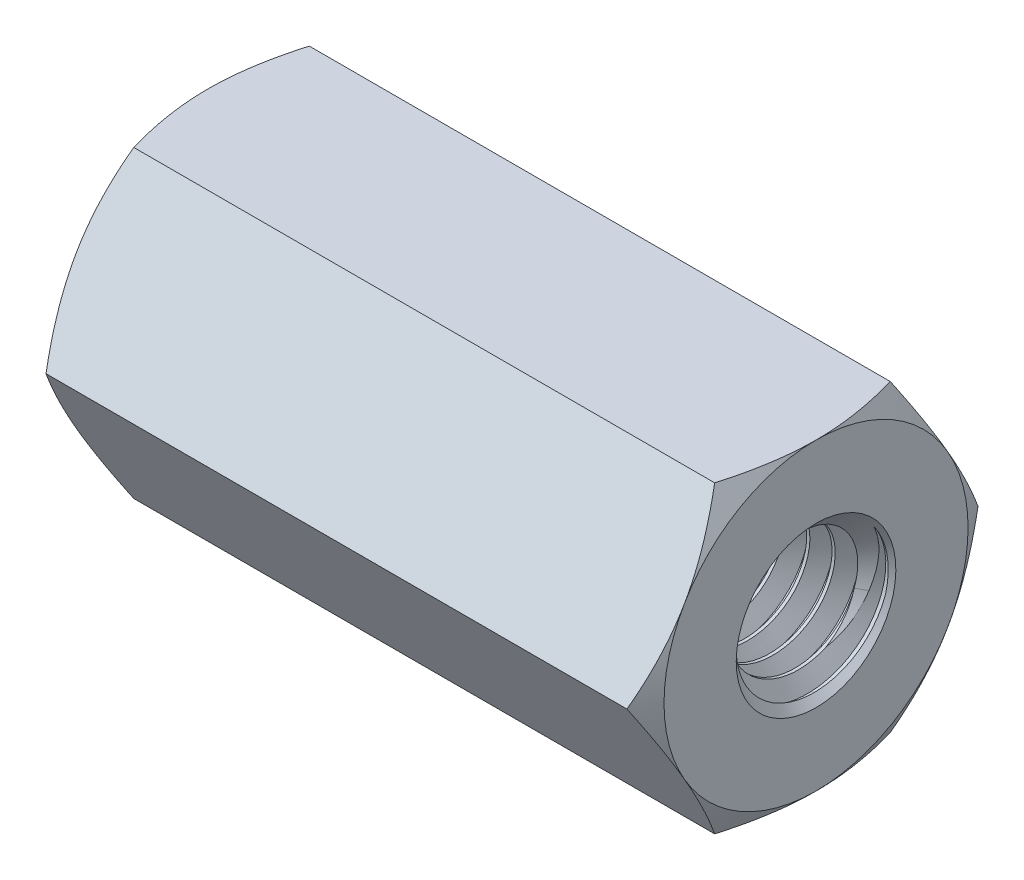
SolidWorks part; units mm, degrees
note: '?' marks a value the reader was unsure of.
material "6061-T6 (SS)"
ref_plane "Front Plane" through (0, 0, 0) normal (0, 0, 1) x (1, 0, 0)
ref_plane "Top Plane" through (0, 0, 0) normal (0, 1, 0) x (1, 0, 0)
ref_plane "Right Plane" through (0, 0, 0) normal (1, 0, 0) x (0, 0, -1)
sketch "Sketch1" plane through (0, 0, 0) normal (0, 0, 1) x (1, 0, 0)
  line L0 (0, 0) -> (12, 0) construction
  line L1 (0, 3) -> (0, -3) construction
  line L3 (0, 1.5) -> (-0.5, 1.5) construction
  line L4 (0, 3) -> (12, 3) construction
  point P6 (0, 0)
  dimension "Hex" = 6
  dimension "Pitch" = 0.5
  dimension "Thread OD" = 3
  dimension "Length" = 12
sketch "Sketch2" plane through (0, 0, 0) normal (1, 0, 0) x (0, 0, -1)
  line L0 (0, 0) -> (-1.0607, -1.0607) construction
  line L1 (1.7321, 3) -> (-1.7321, 3)
  line L2 (-1.7321, 3) -> (-3.4641, 0)
  line L3 (-3.4641, 0) -> (-1.7321, -3)
  line L4 (-1.7321, -3) -> (1.7321, -3)
  line L5 (1.7321, -3) -> (3.4641, 0)
  line L6 (3.4641, 0) -> (1.7321, 3)
  circle A0 centre (0, 0) radius 3 construction
  circle A1 centre (0, 0) radius 1.5 construction
  dimension "D1" = 45
extrude "Boss-Extrude1" add sketch "Sketch2" along normal up to vertex (12 mm away) up to point (12, 0, 0)
sketch "Sketch3" plane through (0, 0, 0) normal (0, 0, 1) x (1, 0, 0)
  line L0 (0, 1.575) -> (0.075, 1.5)
  line L1 (0, 0) -> (12, 0)
  line L2 (0, 0) -> (0, 1.575)
  line L3 (0.075, 1.5) -> (11.925, 1.5)
  line L4 (12, 0) -> (12, 1.575)
  line L9 (0, 3) -> (0, -3) construction
  line L11 (11.925, 1.5) -> (12, 1.575)
  line L12 (12, 3) -> (12, 0) construction
  line L13 (0, 0) -> (12, 0) construction
  line L14 (0, 1.5) -> (-0.5, 1.5) construction
  dimension "D1" = 3.15
  dimension "D2" = 45
revolve "Cut-Revolve1" cut sketch "Sketch3" angle 360 about L13
sketch "Sketch4" plane through (0, 0, 0) normal (-1, 0, 0) x (0, 0, 1)
  circle A0 centre (0, 0) radius 3
  circle A1 centre (0, 0) radius 3 construction
extrude "Cut-Extrude1" cut sketch "Sketch4" against normal through all draft 60 flip side to cut
sketch "Sketch5" plane through (12, 0, 0) normal (1, 0, 0) x (0, 0, -1)
  circle A0 centre (0, 0) radius 3
  circle A1 centre (0, 0) radius 3 construction
extrude "Cut-Extrude2" cut sketch "Sketch5" against normal through all draft 60 flip side to cut
ref_axis "Center Axis 1" through (0, 0, 0) along (1, 0, 0)?
sketch "Sketch6" plane through (0, 0, 0) normal (0, 0, 1) x (1, 0, 0)
  line L0 (-0.4278, 1.5) -> (-0.2139, 1.1295) construction
  line L1 (-0.2139, 1.1295) -> (0, 1.5) construction
  line L2 (0, 1.5) -> (-0.4278, 1.5) construction
  line L3 (0, 1.5) -> (-0.5, 1.5) construction
  line L5 (-0.4278, 1.5) -> (-0.4639, 1.5625) construction
  line L6 (-0.4639, 1.5625) -> (0.0361, 1.5625) construction
  line L7 (0.0361, 1.5625) -> (0, 1.5) construction
  line L8 (-0.2452, 1.1836) -> (-0.1827, 1.1836) construction
  line L9 (-0.2139, 1.5) -> (-0.2139, 1.5625) construction
  line L10 (-0.4459, 1.5312) -> (0.018, 1.5312)
  line L11 (0.018, 1.5312) -> (-0.1827, 1.1836)
  line L12 (-0.1827, 1.1836) -> (-0.2452, 1.1836)
  line L13 (-0.2452, 1.1836) -> (-0.4459, 1.5312)
  dimension "D1" = 0.0625
sketch "Sketch7" plane through (0, 0, 0) normal (-1, 0, 0) x (0, 0, 1)
  line L0 (0, 3) -> (0, -3) construction
  circle A0 centre (0, 0) radius 1.5
curve "Helix/Spiral1" pitch 0.5 height 12.5 turns 25
sweep "Sweep1" add profiles "Sketch6" path "Helix/Spiral1"
sketch "Sketch8" plane through (0, 0, 0) normal (-1, 0, 0) x (0, 0, 1)
  circle A0 centre (0, 0) radius 1.575
extrude "Cut-Extrude3" cut sketch "Sketch8" against normal through all draft 45 and the other way through all draft 45
sketch "Sketch9" plane through (12, 0, 0) normal (1, 0, 0) x (0, 0, -1)
  circle A0 centre (0, 0) radius 1.575
  circle A1 centre (0, 0) radius 1.575 construction
extrude "Cut-Extrude4" cut sketch "Sketch9" against normal through all draft 45 and the other way through all draft 45
equation "\"D1@Sketch3\"=\"Thread OD@Sketch1\"*1.05"
equation "\"D1@Sketch6\"=\"Pitch@Sketch1\"/8"
equation "\"D4@Helix/Spiral1\"=\"Pitch@Sketch1\""
equation "\"D3@Helix/Spiral1\"=\"Pitch@Sketch1\"+\"Length@Sketch1\""
